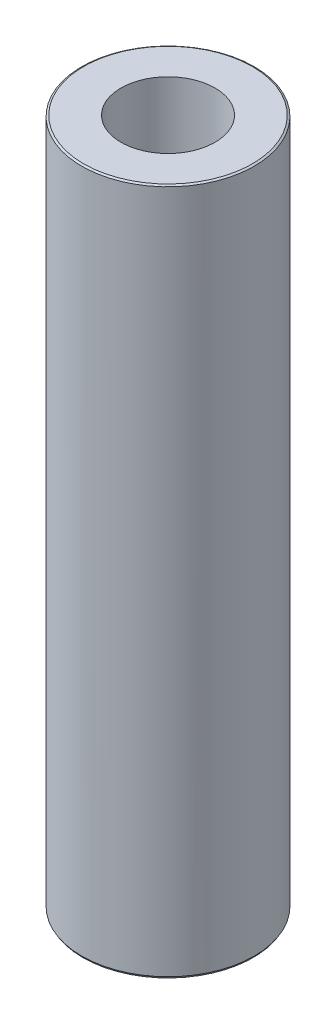
SolidWorks part; units mm, degrees
ref_plane "Front Plane" through (0, 0, 0) normal (0, 0, 1) x (1, 0, 0)
ref_plane "Top Plane" through (0, 0, 0) normal (0, 1, 0) x (1, 0, 0)
ref_plane "Right Plane" through (0, 0, 0) normal (1, 0, 0) x (0, 0, -1)
sketch "Sketch1" plane through (0, 0, 0) normal (0, 1, 0) x (1, 0, 0)
  circle A0 centre (0, 0) radius 45
  dimension "SHAFT_OD" = 90
extrude "Boss-Extrude1" add sketch "Sketch1" along normal blind 358.492
sketch "Sketch2" plane through (0, 0, 0) normal (0, 1, 0) x (1, 0, 0)
  circle A0 centre (0, 0) radius 24.5483
  dimension "BORE_D" = 49.0967
extrude "Cut-Extrude1" cut sketch "Sketch2" along normal through all
chamfer "Chamfer1" distance 0.5714 angle 60 2 edges at (0, 358.492, 45) (0, 0, 45) first distance on face at (0, 358.492, 45) first distance on face at (0, 0, 24.5483)
